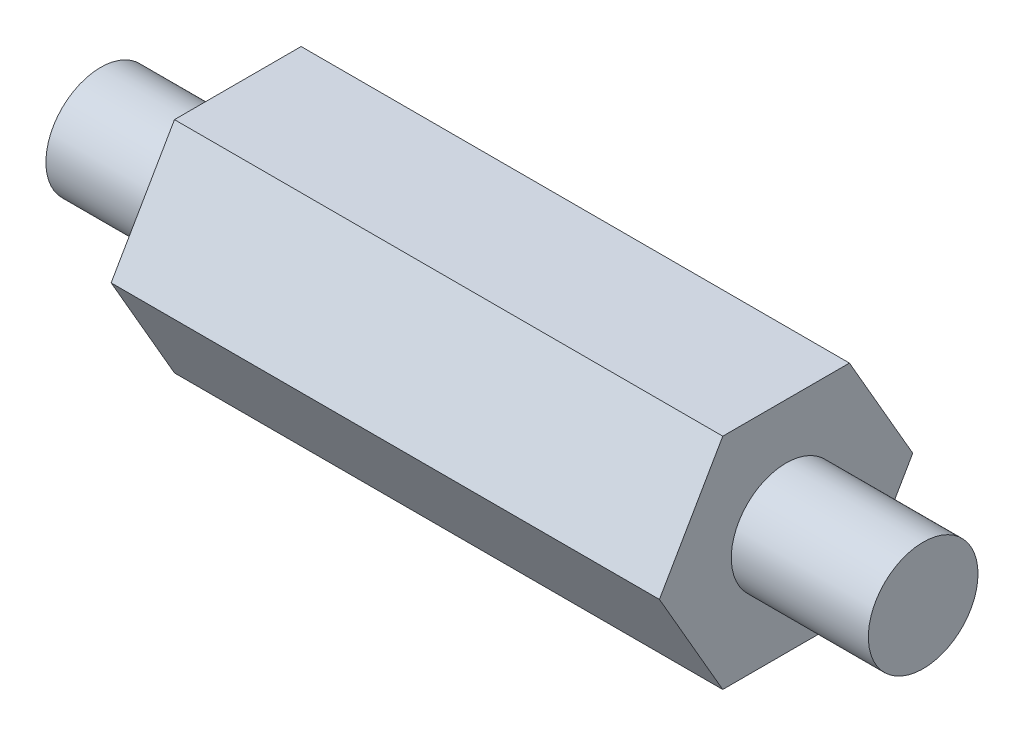
SolidWorks part; units mm, degrees
ref_plane "Plan de face" through (0, 0, 0) normal (0, 0, 1) x (1, 0, 0)
ref_plane "Plan de dessus" through (0, 0, 0) normal (0, 1, 0) x (1, 0, 0)
ref_plane "Plan de droite" through (0, 0, 0) normal (1, 0, 0) x (0, 0, -1)
sketch "Esquisse1" plane through (0, 0, 0) normal (1, 0, 0) x (0, 0, -1)
  line L0 (-2.31, 4.001) -> (2.31, 4.001)
  line L1 (2.31, 4.001) -> (4.62, 0)
  line L2 (4.62, 0) -> (2.31, -4.001)
  line L3 (2.31, -4.001) -> (-2.31, -4.001)
  line L4 (-2.31, -4.001) -> (-4.62, 0)
  line L5 (-4.62, 0) -> (-2.31, 4.001)
  line L6 (0, 0) -> (-4.62, 0) construction
  circle A0 centre (0, 0) radius 4.62
  circle A1 centre (0, 0) radius 2
  dimension "D1" = 9.24
  dimension "D2" = 4
extrude "Boss.-Extru.1" add sketch "Esquisse1" along normal mid plane 30 contours A1 region at (0, 0, 0)
extrude "Boss.-Extru.2" add sketch "Esquisse1<4>" along normal mid plane 20 contours A1 L4 L3 L2 L1 L0 L5 region at (0, 3.8788, 0)
sketch "Esquisse1<4>" plane through (0, 0, 0) normal (1, 0, 0) x (0, 0, -1) same geometry as "Esquisse1"
